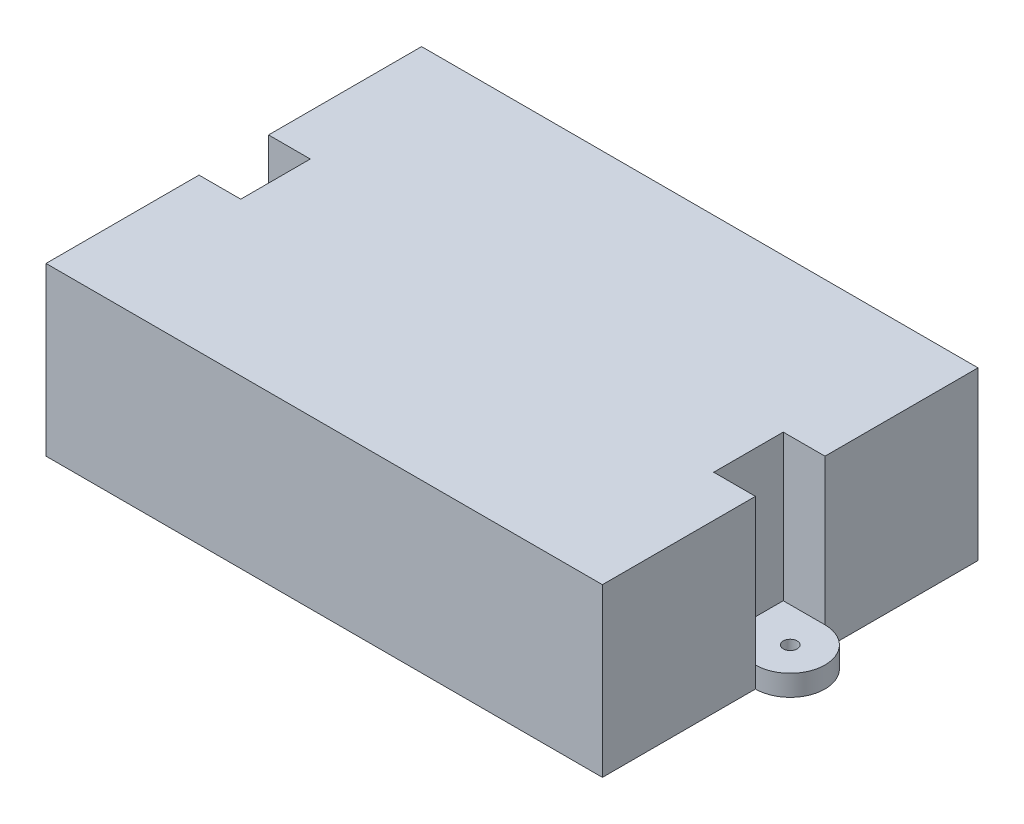
SolidWorks part; units mm, degrees
ref_plane "Front Plane" through (0, 0, 0) normal (0, 0, 1) x (1, 0, 0)
ref_plane "Top Plane" through (0, 0, 0) normal (0, 1, 0) x (1, 0, 0)
ref_plane "Right Plane" through (0, 0, 0) normal (1, 0, 0) x (0, 0, -1)
sketch "Sketch1" plane through (0, 0, 0) normal (0, 1, 0) x (1, 0, 0)
  line L0 (-40, 5) -> (-40, 27)
  line L1 (-40, -27) -> (40, -27)
  line L2 (-40, -27) -> (-40, -5)
  line L3 (-40, 27) -> (40, 27)
  line L4 (40, -27) -> (40, -5)
  line L5 (-40, -27) -> (40, 27) construction
  line L6 (-40, 27) -> (40, -27) construction
  line L7 (40, 5) -> (40, 27)
  arc A0 (40, -5) -> (40, 5) centre (40, 0) ccw
  arc A1 (-40, 5) -> (-40, -5) centre (-40, 0) ccw
  circle A2 centre (-40, 0) radius 1
  circle A3 centre (40, 0) radius 1
  point P0 (0, 0)
  dimension "D3" = 10
  dimension "D4" = 10
  dimension "D5" = 2
  dimension "D6" = 2
  dimension "D1" = 54
  dimension "D2" = 80
extrude "Boss-Extrude1" add sketch "Sketch1" along normal blind 3
sketch "Sketch2" plane through (0, 3, 0) normal (0, 1, 0) x (1, 0, 0)
  line L3 (-40, 5) -> (-34, 5)
  line L4 (-40, -5) -> (-34, -5)
  line L5 (-34, 5) -> (-34, -5)
  line L6 (40, 5) -> (40, 27)
  line L7 (40, 27) -> (-40, 27)
  line L8 (-40, 27) -> (-40, 5)
  line L9 (-40, -5) -> (-40, -27)
  line L10 (-40, -27) -> (40, -27)
  line L11 (40, -27) -> (40, -5)
  line L12 (40, 5) -> (40, 27)
  line L13 (40, 27) -> (-40, 27)
  line L14 (-40, 27) -> (-40, 5)
  line L15 (-40, -5) -> (-40, -27)
  line L16 (-40, -27) -> (40, -27)
  line L17 (40, -27) -> (40, -5)
  line L19 (40, 5) -> (34, 5)
  line L20 (40, -5) -> (34, -5)
  line L21 (34, 5) -> (34, -5)
  arc A2 (-40, 5) -> (-40, -5) centre (-40, 0) ccw
  arc A3 (40, -5) -> (40, 5) centre (40, 0) ccw
  dimension "D4" = 10
  dimension "D2" = 6
  dimension "D3" = 6
  dimension "D5" = 10
extrude "Boss-Extrude2" add sketch "Sketch2" along normal blind 21
equation "\"length\" = 80"
equation "\"width\"= 54"
equation "\"height\" = 24 - \"base_height\""
equation "\"D1@Sketch1\"=\"width\""
equation "\"D2@Sketch1\"=\"length\""
equation "\"D1@Boss-Extrude1\"=\"base_height\""
equation "\"hole_radius\"= 1"
equation "\"base_radius\"= 5"
equation "\"base_height\"= 3"
equation "\"indent_depth\"= 6"
equation "\"D2@Sketch2\"=\"indent_depth\""
equation "\"D3@Sketch2\"=\"indent_depth\""
equation "\"D4@Sketch2\"=\"base_radius\"*2"
equation "\"D5@Sketch2\"=\"base_radius\"*2"
equation "\"D1@Boss-Extrude2\"=\"height\""
